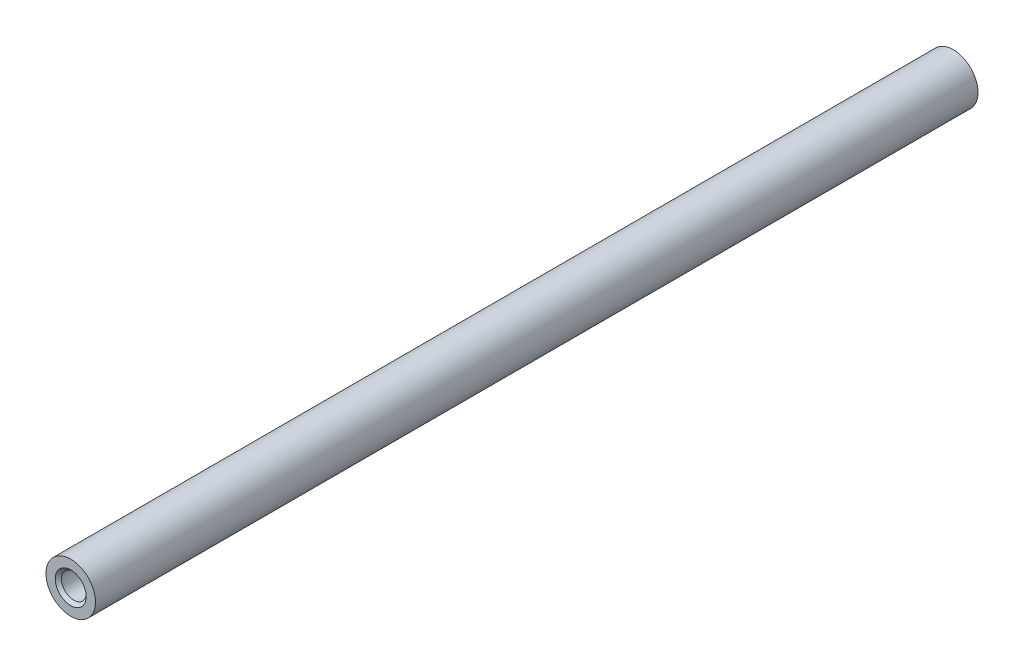
SolidWorks part; units mm, degrees
material "1.0545 (S355N)"
ref_plane "Płaszczyzna przednia" through (0, 0, 0) normal (0, 0, 1) x (1, 0, 0)
ref_plane "Płaszczyzna górna" through (0, 0, 0) normal (0, 1, 0) x (1, 0, 0)
ref_plane "Płaszczyzna prawa" through (0, 0, 0) normal (1, 0, 0) x (0, 0, -1)
sketch "Szkic1" plane through (0, 0, 0) normal (0, 0, 1) x (1, 0, 0)
  circle A0 centre (0, 0) radius 8
  circle A1 centre (0, 0) radius 4
  dimension "D1" = 4
  dimension "D2" = 16
extrude "Dodanie-wyciągnięcie1" add sketch "Szkic1" along normal mid plane 285
sketch "Szkic2" plane through (0, 0, -142.5) normal (0, 0, -1) x (-1, 0, 0)
  circle A0 centre (0, 0) radius 5
  circle A1 centre (0, 0) radius 4 construction
  dimension "D1" = 1
extrude "Wytnij-wyciągnięcie1" cut sketch "Szkic2" against normal blind 30
chamfer "Sfazowanie1" distance 1 angle 45 1 edges at (4, 0, 142.5)
